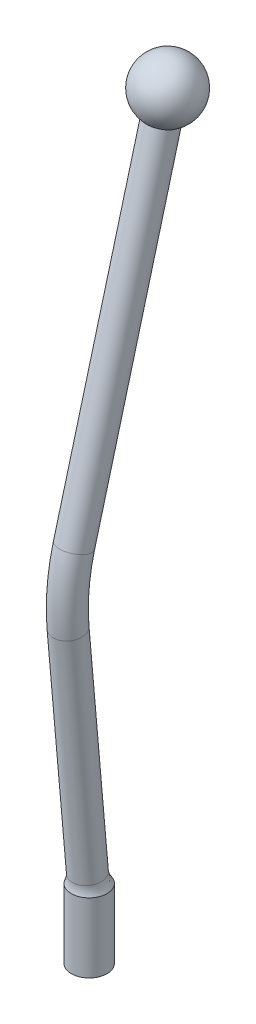
SolidWorks part; units mm, degrees
ref_plane "前视基准面" through (0, 0, 0) normal (0, 0, 1) x (1, 0, 0)
ref_plane "上视基准面" through (0, 0, 0) normal (0, 1, 0) x (1, 0, 0)
ref_plane "右视基准面" through (0, 0, 0) normal (1, 0, 0) x (0, 0, -1)
other "Configuration Table"
sketch "草图1" plane through (0, 0, 0) normal (0, 1, 0) x (1, 0, 0)
  circle A0 centre (0, 0) radius 0.9
  dimension "D1" = 1.8
extrude "凸台-拉伸1" add sketch "草图1" along normal blind 3.5
sketch "草图2" plane through (0, 0, 0) normal (1, 0, 0) x (0, 0, -1)
  line L0 (3.9562, 36.2652) -> (-0.7638, 18.6499)
  line L1 (-1.0665, 15.1902) -> (0, 3)
  line L3 (0.9, 3.5) -> (-0.9, 3.5) construction
  arc A0 (-1.0665, 15.1902) -> (-0.7638, 18.6499) centre (8.8954, 16.0617) cw
  point P21 (-1.2202, 16.9467)
  dimension "D6" = 10
  dimension "D1" = 0.5
  dimension "D2" = 160
  dimension "D3" = 14
  dimension "D4" = 20
  dimension "D5" = 95
ref_plane "基准面1" through (0, 3, 0) normal (0, -0.9962, -0.0872) x (-1, 0, 0)
sweep "扫描1" add path "草图2" circular profile diameter 1.5 parameters "D3"=1.5
sketch "草图20" plane through (0, 34.825, -9.3313) normal (0, 0.9659, -0.2588) x (1, 0, 0)
  line L0 (0, -5.5647) -> (-1.5, -5.5647) construction
  circle A0 centre (0, -5.5647) radius 1.5
  circle A1 centre (0, -5.5647) radius 0.75 construction
  dimension "D1" = 3
revolve "旋转7" add sketch "草图20" angle 360 about L0 region at (0, 35.888, -5.3641)
fillet "圆角2" radius 1 1 edges at (0, 3.5, -0.7091)
